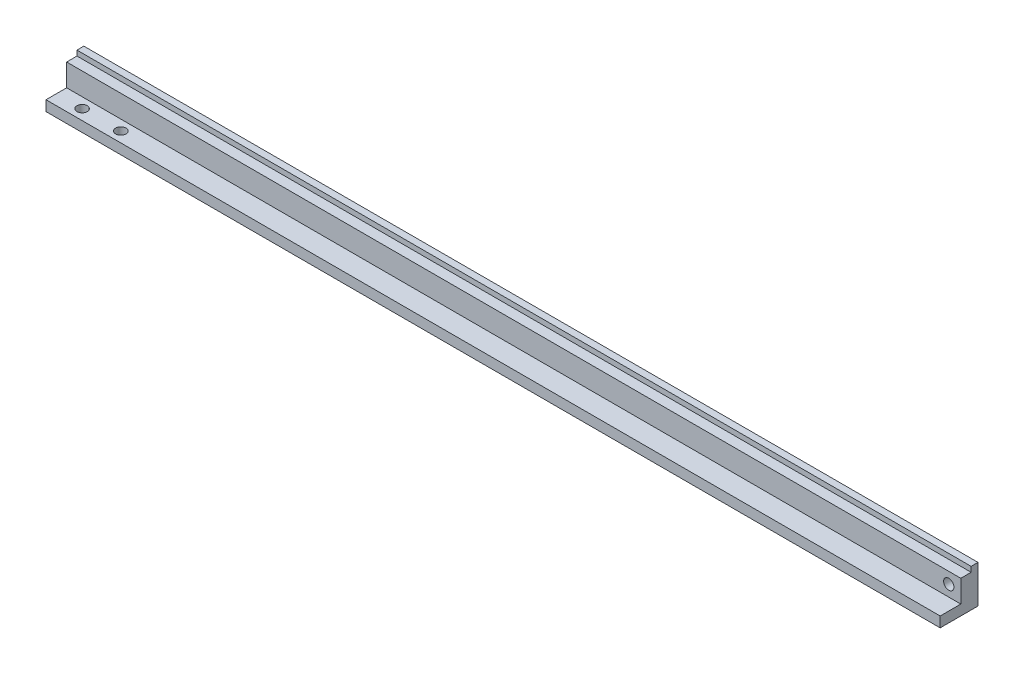
SolidWorks part; units mm, degrees
ref_plane "Спереди" through (0, 0, 0) normal (0, 0, 1) x (1, 0, 0)
ref_plane "Сверху" through (0, 0, 0) normal (0, 1, 0) x (1, 0, 0)
ref_plane "Справа" through (0, 0, 0) normal (1, 0, 0) x (0, 0, -1)
sketch "Эскиз1" plane through (0, 0, 0) normal (1, 0, 0) x (0, 0, -1)
  line L0 (0, 0) -> (-11, 0)
  line L1 (-11, 0) -> (-11, 3)
  line L2 (-11, 3) -> (-5, 3)
  line L3 (-5, 3) -> (-5, 9.5)
  line L4 (-5, 9.5) -> (-2, 9.5)
  line L5 (-2, 9.5) -> (-2, 11)
  line L6 (-2, 11) -> (0, 11)
  line L7 (0, 11) -> (0, 0)
  dimension "D1" = 5
  dimension "D2" = 11
  dimension "D3" = 3
  dimension "D4" = 6
  dimension "D5" = 6.5
  dimension "D6" = 11
  dimension "D7" = 1.5
  dimension "D8" = 2
extrude "Бобышка-Вытянуть1" add sketch "Эскиз1" along normal blind 260
sketch "Эскиз2" plane through (0, 0, 5) normal (0, 0, 1) x (1, 0, 0)
  line L1 (260, 9.5) -> (0, 9.5) construction
  line L2 (260, 9.5) -> (260, 3) construction
  circle A0 centre (256.5, 6.25) radius 1.5
  dimension "D1" = 3
  dimension "D2" = 3.5
  dimension "D3" = 3.25
extrude "Вырез-Вытянуть1" cut sketch "Эскиз2" against normal through all
sketch "Эскиз3" plane through (0, 3, 0) normal (0, 1, 0) x (1, 0, 0)
  line L1 (0, -5) -> (0, -11) construction
  line L2 (260, -11) -> (0, -11) construction
  circle A0 centre (7.5, -8) radius 1.5
  circle A1 centre (18.75, -8) radius 1.5
  dimension "D1" = 3
  dimension "D2" = 3
  dimension "D3" = 7.5
  dimension "D4" = 18.75
  dimension "D5" = 3
  dimension "D6" = 3
extrude "Вырез-Вытянуть2" cut sketch "Эскиз3" against normal through all
